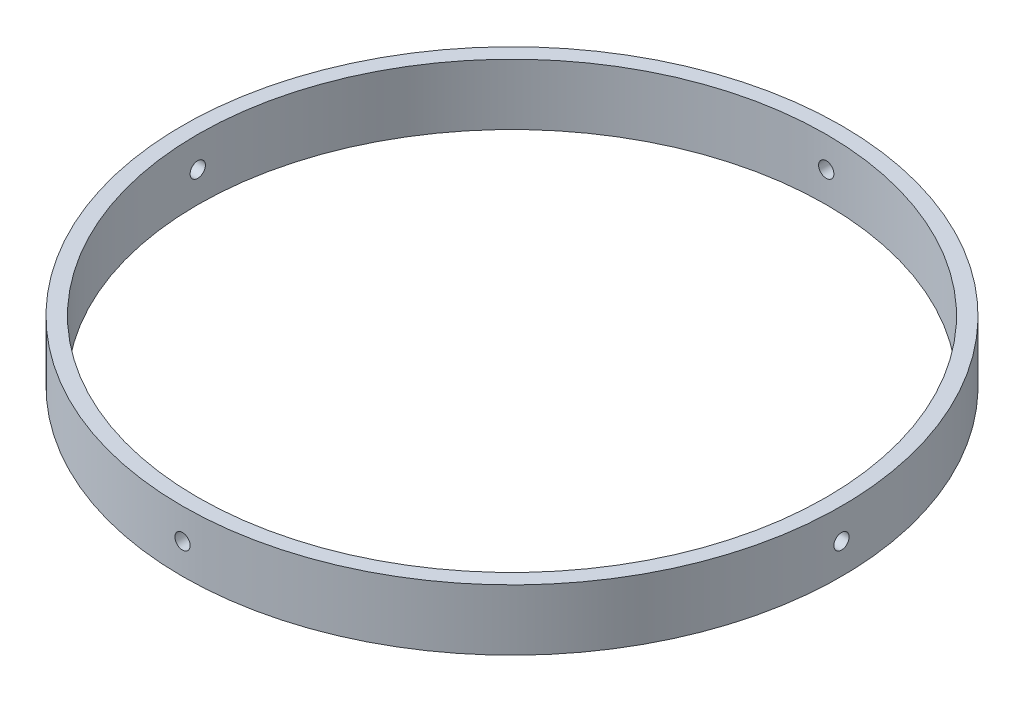
SolidWorks part; units mm, degrees
ref_plane "Front Plane" through (0, 0, 0) normal (0, 0, 1) x (1, 0, 0)
ref_plane "Top Plane" through (0, 0, 0) normal (0, 1, 0) x (1, 0, 0)
ref_plane "Right Plane" through (0, 0, 0) normal (1, 0, 0) x (0, 0, -1)
sketch "Sketch1" plane through (0, 0, 0) normal (0, 1, 0) x (1, 0, 0)
  circle A0 centre (0, 0) radius 68.707
  circle A1 centre (0, 0) radius 65.532
  dimension "D1" = 131.064
  dimension "D2" = 3.175
extrude "Boss-Extrude1" add sketch "Sketch1" along normal blind 12.7
sketch "Sketch2" plane through (0, 0, 0) normal (0, 0, 1) x (1, 0, 0)
  line L0 (0, 0) -> (0, 12.7) construction
  line L1 (65.532, 12.7) -> (-65.532, 12.7) construction
  circle A0 centre (0, 6.35) radius 1.5875
  point P7 (0, 6.35)
  dimension "D1" = 3.175
extrude "Cut-Extrude1" cut sketch "Sketch2" against normal up to surface (68.6887 mm away) up to face at (0, 12.7, 68.707)
pattern_circular "CirPattern1" count 4 over 360 about axis through (0, 12.7, 0) along (0, -1, 0) of "Cut-Extrude1" reverse direction yes
